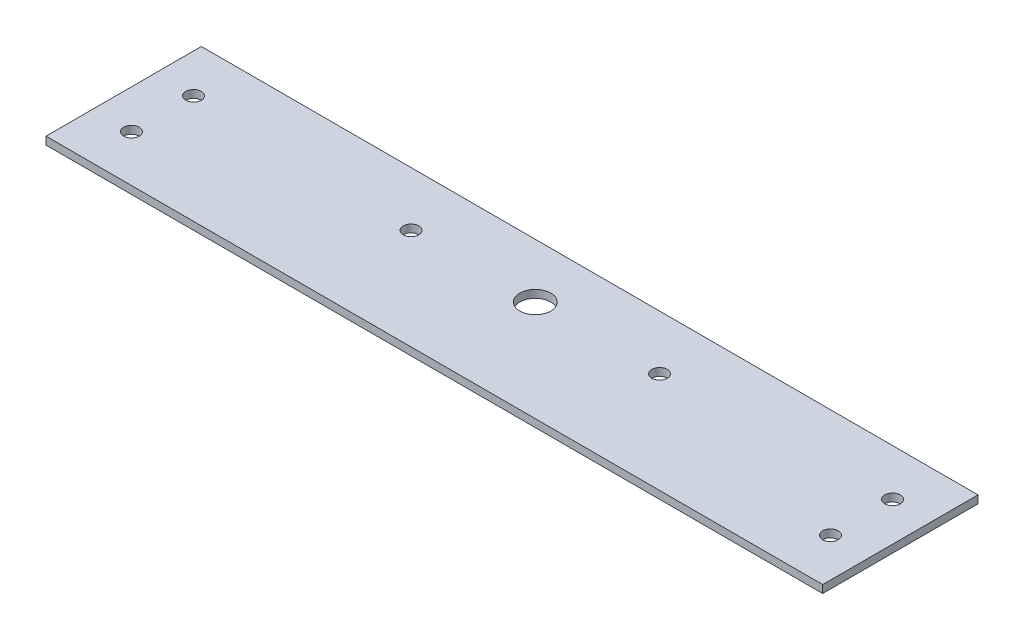
SolidWorks part; units mm, degrees
ref_plane "Front Plane" through (0, 0, 0) normal (0, 0, 1) x (1, 0, 0)
ref_plane "Top Plane" through (0, 0, 0) normal (0, 1, 0) x (1, 0, 0)
ref_plane "Right Plane" through (0, 0, 0) normal (1, 0, 0) x (0, 0, -1)
sketch "Sketch1" plane through (0, 0, 0) normal (0, 1, 0) x (1, 0, 0)
  line L1 (0, 0) -> (500, 0)
  line L2 (0, 0) -> (0, 100)
  line L3 (0, 100) -> (500, 100)
  line L4 (500, 0) -> (500, 100)
  dimension "D1" = 500
  dimension "D2" = 100
extrude "Boss-Extrude1" add sketch "Sketch1" along normal blind 5 contours L3 L4 L1 L2
sketch "Sketch3" plane through (0, 5, 0) normal (0, 1, 0) x (1, 0, 0)
  line L0 (0, 100) -> (500, 100) construction
  circle A0 centre (250, 65) radius 10
  dimension "D1" = 35
extrude "Cut-Extrude1" cut sketch "Sketch3" against normal through all
sketch "Sketch4" plane through (0, 5, 0) normal (0, 1, 0) x (1, 0, 0)
  line L0 (0, 100) -> (500, 100) construction
  circle A0 centre (170, 65) radius 5
  dimension "D1" = 35
extrude "Cut-Extrude2" cut sketch "Sketch4" against normal through all
sketch "Sketch5" plane through (0, 5, 0) normal (0, 1, 0) x (1, 0, 0)
  line L0 (0, 100) -> (500, 100) construction
  circle A0 centre (330, 65) radius 5
  dimension "D1" = 35
extrude "Cut-Extrude3" cut sketch "Sketch5" against normal through all
sketch "Sketch7" plane through (0, 0, 0) normal (0, -1, 0) x (-1, 0, 0)
  line L0 (0, 100) -> (-500, 100) construction
  line L1 (0, 0) -> (-500, 0) construction
  line L2 (-500, 0) -> (-500, 100) construction
  line L3 (0, 0) -> (0, 100) construction
  circle A0 centre (-475, 70) radius 5
  circle A1 centre (-475, 30) radius 5
  circle A2 centre (-25, 30) radius 5
  circle A3 centre (-25, 70) radius 5
  dimension "D1" = 40
  dimension "D3" = 30
  dimension "D2" = 40
  dimension "D4" = 30
  dimension "D5" = 30
  dimension "D6" = 30
  dimension "D7" = 25
  dimension "D8" = 25
  dimension "D9" = 450
extrude "Cut-Extrude4" cut sketch "Sketch7" against normal through all
